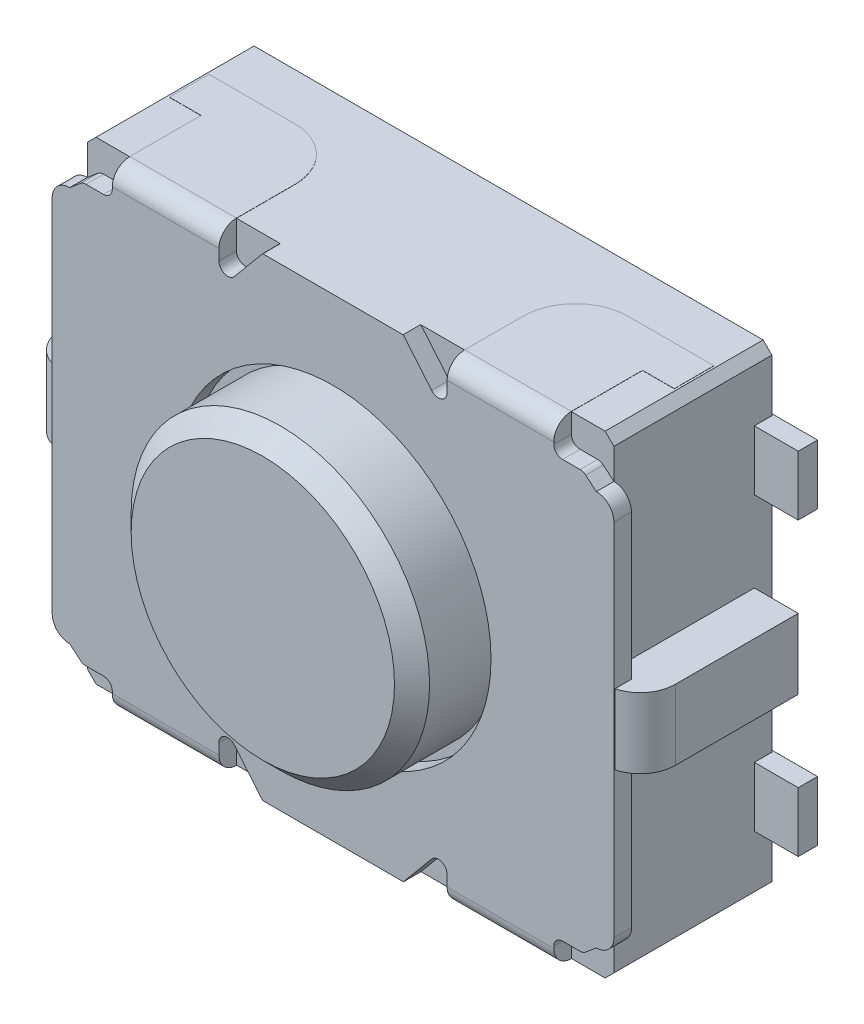
SolidWorks part; units mm, degrees
ref_plane "Front Plane" through (0, 0, 0) normal (0, 0, 1) x (1, 0, 0)
ref_plane "Top Plane" through (0, 0, 0) normal (0, 1, 0) x (1, 0, 0)
ref_plane "Right Plane" through (0, 0, 0) normal (1, 0, 0) x (0, 0, -1)
sketch "Sketch2" plane through (0, 0, 0) normal (0, 0, 1) x (1, 0, 0)
  line L1 (-1.5, 1.35) -> (1.5, 1.35)
  line L2 (-1.5, 1.35) -> (-1.5, -1.35)
  line L3 (-1.5, -1.35) -> (1.5, -1.35)
  line L4 (1.5, 1.35) -> (1.5, -1.35)
  line L5 (-1.5, 1.35) -> (1.5, -1.35) construction
  line L6 (-1.5, -1.35) -> (1.5, 1.35) construction
  point P0 (0, 0)
  dimension "D1" = 3
  dimension "D2" = 2.7
extrude "Boss-Extrude1" add sketch "Sketch2" along normal blind 1
sketch "Sketch3" plane through (0, 0, 1) normal (0, 0, 1) x (1, 0, 0)
  circle A0 centre (0, 0) radius 0.85
  dimension "D1" = 1.7
extrude "Boss-Extrude2" add sketch "Sketch3" along normal blind 0.4
sketch "Sketch4" plane through (0, 0, 0) normal (0, 0, -1) x (-1, 0, 0)
  line L0 (0, 1.7624) -> (0, -1.4276) construction
  line L1 (2.3994, 0) -> (-1.874, 0) construction
  line L2 (-1.25, 0.66) -> (-1.75, 0.66)
  line L3 (-1.25, -1) -> (-1.75, -1)
  line L4 (-1.25, -1) -> (-1.25, -0.66)
  line L5 (-1.25, -0.66) -> (-1.75, -0.66)
  line L6 (-1.75, -1) -> (-1.75, -0.66)
  line L7 (-1.75, 1) -> (-1.75, 0.66)
  line L8 (-1.25, 1) -> (-1.75, 1)
  line L9 (-1.25, 1) -> (-1.25, 0.66)
  line L10 (1.25, -0.66) -> (1.75, -0.66)
  line L11 (1.75, -1) -> (1.75, -0.66)
  line L12 (1.25, -1) -> (1.75, -1)
  line L13 (1.25, -1) -> (1.25, -0.66)
  line L14 (1.25, 1) -> (1.25, 0.66)
  line L15 (1.25, 1) -> (1.75, 1)
  line L16 (1.75, 1) -> (1.75, 0.66)
  line L17 (1.25, 0.66) -> (1.75, 0.66)
  point P9 (-1.25, -0.83)
  dimension "D1" = 0.66
  dimension "D2" = 1
  dimension "D3" = 1.25
  dimension "D4" = 1.75
extrude "Boss-Extrude3" add sketch "Sketch4" along normal blind 0.01 and the other way blind 0.1
chamfer "Chamfer1" distance 0.1 angle 45 1 edges at (0.85, 0, 1.4)
sketch "Sketch5" plane through (0, 0, 1) normal (0, 0, 1) x (1, 0, 0)
  line L0 (0, -2.6561) -> (0, 2.1442) construction
  line L1 (-3.7475, 0) -> (3.7089, 0) construction
  line L2 (0.4, -1.35) -> (0.5616, -1.1561)
  line L3 (-1.5, -1.35) -> (1.5, -1.35) construction
  line L4 (0.65, -1.1881) -> (0.65, -1.35)
  line L5 (0.65, -1.35) -> (0.4, -1.35)
  line L6 (-0.65, -1.1881) -> (-0.65, -1.35)
  line L7 (-0.4, -1.35) -> (-0.5616, -1.1561)
  line L8 (-0.65, -1.35) -> (-0.4, -1.35)
  line L9 (0.65, 1.1881) -> (0.65, 1.35)
  line L10 (0.4, 1.35) -> (0.5616, 1.1561)
  line L11 (0.65, 1.35) -> (0.4, 1.35)
  line L12 (-0.4, 1.35) -> (-0.5616, 1.1561)
  line L13 (-0.65, 1.35) -> (-0.4, 1.35)
  line L14 (-0.65, 1.1881) -> (-0.65, 1.35)
  line L15 (1.2576, -1.35) -> (1.2576, -1.2381)
  line L16 (1.3076, -1.1881) -> (1.4073, -1.1881)
  line L17 (1.4395, -1.1764) -> (1.5, -1.1256)
  line L18 (1.5, -1.35) -> (1.5, 1.35) construction
  line L19 (1.5, -1.1256) -> (1.5, -1.35)
  line L20 (1.5, -1.35) -> (1.2576, -1.35)
  line L21 (-1.5, -1.1256) -> (-1.5, -1.35)
  line L22 (-1.4395, -1.1764) -> (-1.5, -1.1256)
  line L23 (-1.3076, -1.1881) -> (-1.4073, -1.1881)
  line L24 (-1.2576, -1.35) -> (-1.2576, -1.2381)
  line L25 (-1.5, -1.35) -> (-1.2576, -1.35)
  line L26 (-1.4395, 1.1764) -> (-1.5, 1.1256)
  line L27 (-1.3076, 1.1881) -> (-1.4073, 1.1881)
  line L28 (-1.2576, 1.35) -> (-1.2576, 1.2381)
  line L29 (-1.5, 1.35) -> (-1.2576, 1.35)
  line L30 (-1.5, 1.1256) -> (-1.5, 1.35)
  line L31 (1.5, 1.1256) -> (1.5, 1.35)
  line L32 (1.4395, 1.1764) -> (1.5, 1.1256)
  line L33 (1.3076, 1.1881) -> (1.4073, 1.1881)
  line L34 (1.2576, 1.35) -> (1.2576, 1.2381)
  line L35 (1.5, 1.35) -> (1.2576, 1.35)
  arc A0 (0.5616, -1.1561) -> (0.65, -1.1881) centre (0.6, -1.1881) cw
  arc A1 (-0.5616, -1.1561) -> (-0.65, -1.1881) centre (-0.6, -1.1881) ccw
  arc A2 (0.5616, 1.1561) -> (0.65, 1.1881) centre (0.6, 1.1881) ccw
  arc A3 (-0.5616, 1.1561) -> (-0.65, 1.1881) centre (-0.6, 1.1881) cw
  arc A4 (1.4073, -1.1881) -> (1.4395, -1.1764) centre (1.4073, -1.1381) ccw
  arc A5 (1.2576, -1.2381) -> (1.3076, -1.1881) centre (1.3076, -1.2381) cw
  arc A6 (-1.4073, -1.1881) -> (-1.4395, -1.1764) centre (-1.4073, -1.1381) cw
  arc A7 (-1.2576, -1.2381) -> (-1.3076, -1.1881) centre (-1.3076, -1.2381) ccw
  arc A8 (-1.4073, 1.1881) -> (-1.4395, 1.1764) centre (-1.4073, 1.1381) ccw
  arc A9 (-1.2576, 1.2381) -> (-1.3076, 1.1881) centre (-1.3076, 1.2381) cw
  arc A10 (1.4073, 1.1881) -> (1.4395, 1.1764) centre (1.4073, 1.1381) cw
  arc A11 (1.2576, 1.2381) -> (1.3076, 1.1881) centre (1.3076, 1.2381) ccw
  point P12 (0.65, -1.05)
  dimension "D3" = 0.05
  dimension "D5" = 0.05
  dimension "D1" = 0.4
  dimension "D2" = 0.3
  dimension "D4" = 0.25
extrude "Cut-Extrude1" cut sketch "Sketch5" against normal blind 0.1
sketch "Sketch6" plane through (0, 0, 1) normal (0, 0, 1) x (1, 0, 0)
  line L1 (-1.75, 0.2) -> (1.75, 0.2)
  line L2 (-1.75, 0.2) -> (-1.75, -0.2)
  line L3 (-1.75, -0.2) -> (1.75, -0.2)
  line L4 (1.75, 0.2) -> (1.75, -0.2)
  line L5 (-1.75, 0.2) -> (1.75, -0.2) construction
  line L6 (-1.75, -0.2) -> (1.75, 0.2) construction
  point P0 (0, 0)
  dimension "D1" = 0.4
  dimension "D2" = 3.5
extrude "Boss-Extrude4" add sketch "Sketch6" against normal blind 0.9
sketch "Sketch7" plane through (0, -1.35, 0) normal (0, -1, 0) x (1, 0, 0)
  line L16 (0.65, 0.9) -> (0.65, 0.5688)
  line L17 (0.95, 0.2688) -> (1.4383, 0.2688)
  line L18 (1.4383, 0.2688) -> (1.4383, 0.4943)
  line L19 (1.4383, 0.4943) -> (1.2576, 0.4943)
  line L20 (1.2576, 0.4943) -> (1.2576, 0.9)
  line L21 (0, -0.899) -> (0, 1.7212) construction
  line L22 (-1.2576, 0.4943) -> (-1.2576, 0.9)
  line L23 (-1.4383, 0.4943) -> (-1.2576, 0.4943)
  line L24 (-1.4383, 0.2688) -> (-1.4383, 0.4943)
  line L25 (-0.95, 0.2688) -> (-1.4383, 0.2688)
  line L26 (-0.65, 0.9) -> (-0.65, 0.5688)
  line L32 (1.5, 0.9) -> (1.2576, 0.9)
  line L33 (1.2576, 0.9) -> (1.2576, 1)
  line L34 (1.2576, 1) -> (0.65, 1)
  line L35 (0.65, 1) -> (0.65, 0.9)
  line L36 (0.65, 0.9) -> (0.4, 0.9)
  line L37 (0.4, 0.9) -> (0.4, 1)
  line L38 (0.4, 1) -> (-0.4, 1)
  line L39 (-0.4, 1) -> (-0.4, 0.9)
  line L40 (-0.4, 0.9) -> (-0.65, 0.9)
  line L41 (-0.65, 0.9) -> (-0.65, 1)
  line L42 (-0.65, 1) -> (-1.2576, 1)
  line L43 (-1.2576, 1) -> (-1.2576, 0.9)
  line L44 (-1.2576, 0.9) -> (-1.5, 0.9)
  line L45 (-1.5, 0.9) -> (-1.5, 0)
  line L46 (-1.5, 0) -> (1.5, 0)
  line L47 (1.5, 0) -> (1.5, 0.9)
  line L48 (1.5, 0.9) -> (1.2576, 0.9)
  line L49 (1.2576, 0.9) -> (1.2576, 1)
  line L51 (0.65, 1) -> (0.65, 0.9)
  line L52 (0.65, 0.9) -> (0.4, 0.9)
  line L53 (0.4, 0.9) -> (0.4, 1)
  line L54 (0.4, 1) -> (-0.4, 1)
  line L55 (-0.4, 1) -> (-0.4, 0.9)
  line L56 (-0.4, 0.9) -> (-0.65, 0.9)
  line L57 (-0.65, 0.9) -> (-0.65, 1)
  line L59 (-1.2576, 1) -> (-1.2576, 0.9)
  line L60 (-1.2576, 0.9) -> (-1.5, 0.9)
  line L61 (-1.5, 0.9) -> (-1.5, 0)
  line L62 (-1.5, 0) -> (1.5, 0)
  line L63 (1.5, 0) -> (1.5, 0.9)
  arc A0 (0.65, 0.5688) -> (0.95, 0.2688) centre (0.95, 0.5688) ccw
  arc A1 (-0.65, 0.5688) -> (-0.95, 0.2688) centre (-0.95, 0.5688) cw
  line M23 (1.5, 0.9) -> (1.2576, 0.9)
  line M27 (0.65, 0.9) -> (0.4, 0.9)
  line M28 (0.4, 0.9) -> (0.4, 1)
  line M29 (0.4, 1) -> (-0.4, 1)
  line M30 (-0.4, 1) -> (-0.4, 0.9)
  line M31 (-0.4, 0.9) -> (-0.65, 0.9)
  line M35 (-1.2576, 0.9) -> (-1.5, 0.9)
  line M36 (-1.5, 0.9) -> (-1.5, 0)
  line M37 (-1.5, 0) -> (1.5, 0)
  line M38 (1.5, 0) -> (1.5, 0.9)
  dimension "D2" = 0.3
  dimension "D1" = 0
extrude "Cut-Extrude2" cut sketch "Sketch7" against normal blind 0.001 contours L21 L54 L26 A1 L25 L24 L23 L22 M37 M30 M31 M35 M36 | L21 L62 L20 L19 L18 L17 A0 L16 M38 M23 M27 M28 M29 region at (0.6229, -1.35, 0.4186) region at (-0.6229, -1.35, 0.4186)
sketch "Sketch8" plane through (0, 1.35, 0) normal (0, 1, 0) x (1, 0, 0)
  line L16 (1.4383, -0.2688) -> (1.4383, -0.4943)
  line L17 (1.4383, -0.4943) -> (1.2576, -0.4943)
  line L18 (1.2576, -0.4943) -> (1.2576, -0.9)
  line L19 (1.4383, -0.2688) -> (0.95, -0.2688)
  line L20 (0.65, -0.5688) -> (0.65, -1)
  line L21 (-0.65, -0.5688) -> (-0.65, -0.9)
  line L22 (-1.2576, -0.4943) -> (-1.2576, -0.9)
  line L23 (-1.2576, -0.4943) -> (-1.4383, -0.4943)
  line L24 (-1.4383, -0.4943) -> (-1.4383, -0.2688)
  line L25 (-1.4383, -0.2688) -> (-0.95, -0.2688)
  line L32 (-1.2576, -1) -> (-0.65, -1)
  line L33 (-0.65, -1) -> (-0.65, -0.9)
  line L34 (-0.65, -0.9) -> (-0.4, -0.9)
  line L35 (-0.4, -0.9) -> (-0.4, -1)
  line L36 (-0.4, -1) -> (0.4, -1)
  line L37 (0.4, -1) -> (0.4, -0.9)
  line L38 (0.4, -0.9) -> (0.65, -0.9)
  line L39 (0.65, -0.9) -> (0.65, -1)
  line L40 (0.65, -1) -> (1.2576, -1)
  line L41 (1.2576, -1) -> (1.2576, -0.9)
  line L42 (1.2576, -0.9) -> (1.5, -0.9)
  line L43 (1.5, -0.9) -> (1.5, 0)
  line L44 (1.5, 0) -> (-1.5, 0)
  line L45 (-1.5, 0) -> (-1.5, -0.9)
  line L46 (-1.5, -0.9) -> (-1.2576, -0.9)
  line L47 (-1.2576, -0.9) -> (-1.2576, -1)
  line L48 (-1.2576, -1) -> (-0.65, -1)
  line L49 (-0.65, -1) -> (-0.65, -0.9)
  line L50 (-0.65, -0.9) -> (-0.4, -0.9)
  line L51 (-0.4, -0.9) -> (-0.4, -1)
  line L52 (-0.4, -1) -> (0.4, -1)
  line L53 (0.4, -1) -> (0.4, -0.9)
  line L54 (0.4, -0.9) -> (0.65, -0.9)
  line L55 (0.65, -0.9) -> (0.65, -1)
  line L57 (1.2576, -1) -> (1.2576, -0.9)
  line L58 (1.2576, -0.9) -> (1.5, -0.9)
  line L59 (1.5, -0.9) -> (1.5, 0)
  line L60 (1.5, 0) -> (-1.5, 0)
  line L61 (-1.5, 0) -> (-1.5, -0.9)
  line L62 (-1.5, -0.9) -> (-1.2576, -0.9)
  line L63 (-1.2576, -0.9) -> (-1.2576, -1)
  arc A0 (0.95, -0.2688) -> (0.65, -0.5688) centre (0.95, -0.5688) ccw
  arc A1 (-0.95, -0.2688) -> (-0.65, -0.5688) centre (-0.95, -0.5688) cw
  line M19 (-0.65, -0.9) -> (-0.4, -0.9)
  line M20 (-0.4, -0.9) -> (-0.4, -1)
  line M21 (-0.4, -1) -> (0.4, -1)
  line M22 (0.4, -1) -> (0.4, -0.9)
  line M23 (0.4, -0.9) -> (0.65, -0.9)
  line M27 (1.2576, -0.9) -> (1.5, -0.9)
  line M28 (1.5, -0.9) -> (1.5, 0)
  line M29 (1.5, 0) -> (-1.5, 0)
  line M30 (-1.5, 0) -> (-1.5, -0.9)
  line M31 (-1.5, -0.9) -> (-1.2576, -0.9)
  dimension "D1" = 0
extrude "Cut-Extrude3" cut sketch "Sketch8" against normal blind 0.001 contours L25 A1 L21 L20 A0 L19 L16 L17 L18 L22 L23 L24 M19 M20 M21 M22 M23 M27 M28 M29 M30 M31 region at (0, 1.35, 0.4186)
fillet "Fillet1" radius 0.2 2 edges at (1.75, 0, 1) (-1.75, 0, 1)
sketch "Sketch9" plane through (0, 0, 1) normal (0, 0, 1) x (1, 0, 0)
  circle A0 centre (0, 0) radius 0.85
  circle A1 centre (0, 0) radius 0.9
  dimension "D1" = 1.8
extrude "Cut-Extrude4" cut sketch "Sketch9" against normal blind 0.1
fillet "Fillet2" radius 0.1 4 edges at (0.9538, 1.35, 1) (-0.9538, 1.35, 1) (-0.9538, -1.35, 1) (0.9538, -1.35, 1)
chamfer "Chamfer2" distance 0.05 angle 45 4 edges at (1.5, -1.349, 0.45) (-1.5, -1.349, 0.45) (-1.5, 1.349, 0.45) (1.5, 1.349, 0.45)
sketch "Sketch10" plane through (-1.5, 0, 0) normal (-1, 0, 0) x (0, 0, 1)
  line L1 (1, 1.1256) -> (0.9, 1.1256)
  line L2 (1, 1.1256) -> (1, -1.1256)
  line L3 (1, -1.1256) -> (0.9, -1.1256)
  line L4 (0.9, 1.1256) -> (0.9, -1.1256)
extrude "Boss-Extrude5" add sketch "Sketch10" along normal blind 0.1
fillet "Fillet3" radius 0.1 2 edges at (-1.6, 1.1256, 0.95) (-1.6, -1.1256, 0.95)
sketch "Sketch11" plane through (1.5, 0, 0) normal (1, 0, 0) x (0, 0, -1)
  line L1 (-1, -1.1256) -> (-0.9, -1.1256)
  line L2 (-1, -1.1256) -> (-1, 1.1256)
  line L3 (-1, 1.1256) -> (-0.9, 1.1256)
  line L4 (-0.9, -1.1256) -> (-0.9, 1.1256)
extrude "Boss-Extrude6" add sketch "Sketch11" along normal blind 0.1
fillet "Fillet4" radius 0.1 2 edges at (1.6, 1.1256, 0.95) (1.6, -1.1256, 0.95)
